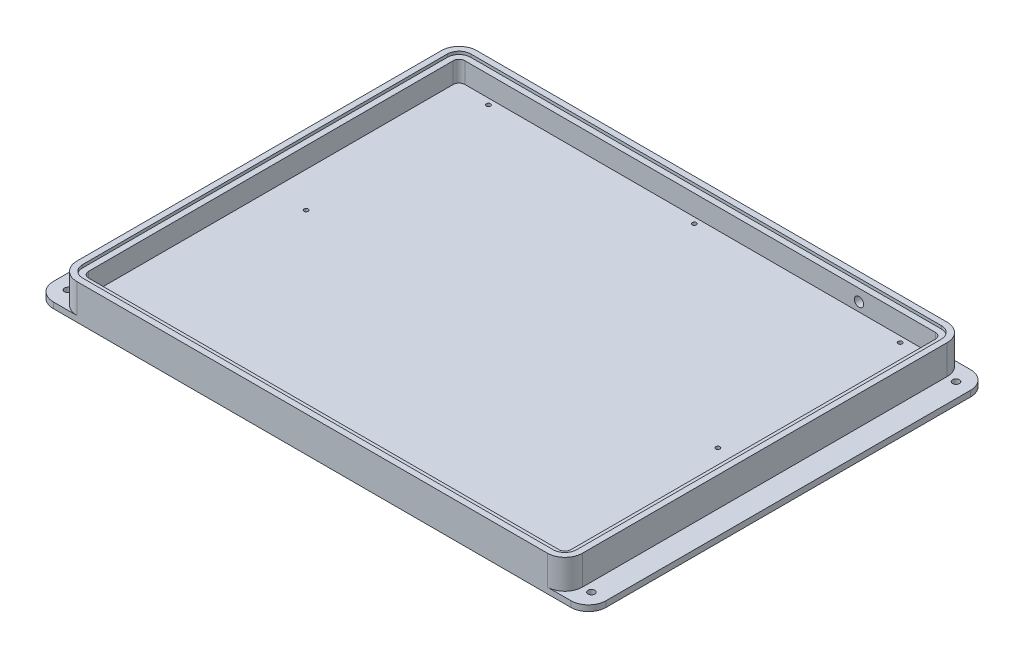
SolidWorks part; units mm, degrees
ref_plane "Front Plane" through (0, 0, 0) normal (0, 0, 1) x (1, 0, 0)
ref_plane "Top Plane" through (0, 0, 0) normal (0, 1, 0) x (1, 0, 0)
ref_plane "Right Plane" through (0, 0, 0) normal (1, 0, 0) x (0, 0, -1)
sketch "Sketch1" plane through (0, 0, 0) normal (0, 1, 0) x (1, 0, 0)
  line L1 (0, 0) -> (273.05, 0)
  line L2 (0, 0) -> (0, 215.9)
  line L3 (0, 215.9) -> (273.05, 215.9)
  line L4 (273.05, 0) -> (273.05, 215.9)
  dimension "D1" = 273.05
  dimension "D2" = 215.9
extrude "Boss-Extrude1" add sketch "Sketch1" along normal blind 19.05
fillet "Fillet1" radius 9.525 4 edges at (273.05, 9.525, 0) (273.05, 9.525, -215.9) (0, 9.525, 0) (0, 9.525, -215.9)
sketch "Sketch3" plane through (0, 19.05, 0) normal (0, 1, 0) x (1, 0, 0)
  line L25 (266.7, 9.525) -> (266.7, 206.375)
  line L26 (9.525, 6.35) -> (263.525, 6.35)
  line L27 (6.35, 206.375) -> (6.35, 9.525)
  line L28 (263.525, 209.55) -> (9.525, 209.55)
  line L29 (266.7, 9.525) -> (266.7, 206.375)
  line L30 (9.525, 6.35) -> (263.525, 6.35)
  line L31 (6.35, 206.375) -> (6.35, 9.525)
  line L32 (263.525, 209.55) -> (9.525, 209.55)
  arc A21 (266.7, 206.375) -> (263.525, 209.55) centre (263.525, 206.375) ccw
  arc A22 (263.525, 6.35) -> (266.7, 9.525) centre (263.525, 9.525) ccw
  arc A23 (6.35, 9.525) -> (9.525, 6.35) centre (9.525, 9.525) ccw
  arc A24 (9.525, 209.55) -> (6.35, 206.375) centre (9.525, 206.375) ccw
  arc A25 (266.7, 206.375) -> (263.525, 209.55) centre (263.525, 206.375) ccw
  arc A26 (263.525, 6.35) -> (266.7, 9.525) centre (263.525, 9.525) ccw
  arc A27 (6.35, 9.525) -> (9.525, 6.35) centre (9.525, 9.525) ccw
  arc A28 (9.525, 209.55) -> (6.35, 206.375) centre (9.525, 206.375) ccw
  dimension "D1" = 6.35
extrude "Cut-Extrude1" cut sketch "Sketch3" against normal blind 12.7
sketch "Sketch4" plane through (0, 19.05, 0) normal (0, 1, 0) x (1, 0, 0)
  line L24 (269.875, 9.525) -> (269.875, 206.375)
  line L25 (9.525, 3.175) -> (263.525, 3.175)
  line L26 (3.175, 206.375) -> (3.175, 9.525)
  line L27 (263.525, 212.725) -> (9.525, 212.725)
  line L28 (269.875, 9.525) -> (269.875, 206.375)
  line L29 (9.525, 3.175) -> (263.525, 3.175)
  line L30 (3.175, 206.375) -> (3.175, 9.525)
  line L31 (263.525, 212.725) -> (9.525, 212.725)
  arc A20 (269.875, 206.375) -> (263.525, 212.725) centre (263.525, 206.375) ccw
  arc A21 (263.525, 3.175) -> (269.875, 9.525) centre (263.525, 9.525) ccw
  arc A22 (3.175, 9.525) -> (9.525, 3.175) centre (9.525, 9.525) ccw
  arc A23 (9.525, 212.725) -> (3.175, 206.375) centre (9.525, 206.375) ccw
  arc A24 (269.875, 206.375) -> (263.525, 212.725) centre (263.525, 206.375) ccw
  arc A25 (263.525, 3.175) -> (269.875, 9.525) centre (263.525, 9.525) ccw
  arc A26 (3.175, 9.525) -> (9.525, 3.175) centre (9.525, 9.525) ccw
  arc A27 (9.525, 212.725) -> (3.175, 206.375) centre (9.525, 206.375) ccw
  dimension "D1" = 3.175
extrude "Cut-Extrude2" cut sketch "Sketch4" against normal blind 1.5875
sketch "Sketch5" plane through (0, 6.35, 0) normal (0, 1, 0) x (1, 0, 0)
  line L0 (136.525, 206.375) -> (136.525, 209.55) construction
  line L1 (25.4, 206.375) -> (247.65, 206.375) construction
  line L2 (25.4, 206.375) -> (25.4, 9.525) construction
  line L3 (25.4, 9.525) -> (247.65, 9.525) construction
  line L4 (247.65, 206.375) -> (247.65, 9.525) construction
  line L5 (263.525, 209.55) -> (9.525, 209.55) construction
  line L6 (25.4, 107.95) -> (6.35, 107.95) construction
  line L7 (6.35, 206.375) -> (6.35, 9.525) construction
  line L8 (247.65, 107.95) -> (266.7, 107.95) construction
  line L9 (266.7, 9.525) -> (266.7, 206.375) construction
  line L10 (136.525, 9.525) -> (136.525, 6.35) construction
  line L11 (263.525, 6.35) -> (9.525, 6.35) construction
  circle A0 centre (25.4, 206.375) radius 1.1303
  circle A1 centre (136.525, 206.375) radius 1.1303
  circle A2 centre (247.65, 206.375) radius 1.1303
  circle A3 centre (247.65, 107.95) radius 1.1303
  circle A4 centre (25.4, 107.95) radius 1.1303
  circle A5 centre (25.4, 9.525) radius 1.1303
  circle A6 centre (136.525, 9.525) radius 1.1303
  circle A7 centre (247.65, 9.525) radius 1.1303
  dimension "D3" = 2.2606
  dimension "D1" = 196.85
  dimension "D2" = 222.25
extrude "Cut-Extrude3" cut sketch "Sketch5" against normal blind 4.7625
sketch "Sketch6" plane through (0, 0, -215.9) normal (0, 0, -1) x (-1, 0, 0)
  line L1 (-273.05, 0) -> (-273.05, 19.05) construction
  line L3 (-263.525, 19.05) -> (-9.525, 19.05) construction
  circle A0 centre (-222.25, 11.1125) radius 2.5
  dimension "D2" = 5
  dimension "D1" = 50.8
  dimension "D3" = 7.9375
extrude "Cut-Extrude4" cut sketch "Sketch6" against normal blind 12.7
sketch "Sketch7" plane through (0, 0, 0) normal (0, -1, 0) x (1, 0, 0)
  line L0 (263.525, -215.9) -> (9.525, -215.9) construction
  line L1 (-3.175, 0) -> (276.225, 0)
  line L2 (-12.7, -9.525) -> (-12.7, -206.375)
  line L3 (-3.175, -215.9) -> (276.225, -215.9)
  line L4 (285.75, -9.525) -> (285.75, -206.375)
  line L5 (9.525, 0) -> (263.525, 0) construction
  line L6 (0, -206.375) -> (0, -9.525) construction
  line L7 (273.05, -9.525) -> (273.05, -206.375) construction
  arc A0 (-12.7, -206.375) -> (-3.175, -215.9) centre (-3.175, -206.375) ccw
  arc A1 (276.225, -215.9) -> (285.75, -206.375) centre (276.225, -206.375) ccw
  arc A2 (276.225, 0) -> (285.75, -9.525) centre (276.225, -9.525) cw
  arc A3 (-3.175, 0) -> (-12.7, -9.525) centre (-3.175, -9.525) ccw
  dimension "D3" = 9.525
  dimension "D1" = 12.7
  dimension "D2" = 12.7
extrude "Boss-Extrude2" add sketch "Sketch7" against normal blind 3.175
sketch "Sketch8" plane through (0, 3.175, 0) normal (0, 1, 0) x (1, 0, 0)
  line L0 (-4.7625, 215.9) -> (-4.7625, 0) construction
  line L1 (-12.7, 9.525) -> (-12.7, 206.375) construction
  line L2 (-3.175, 215.9) -> (9.525, 215.9) construction
  line L3 (285.75, 206.375) -> (285.75, 9.525) construction
  line L4 (-4.7625, 206.375) -> (277.8125, 206.375) construction
  line L5 (-4.7625, 206.375) -> (-4.7625, 9.525) construction
  line L6 (-4.7625, 9.525) -> (277.8125, 9.525) construction
  line L7 (277.8125, 206.375) -> (277.8125, 9.525) construction
  line L8 (9.525, 0) -> (-3.175, 0) construction
  circle A0 centre (-4.7625, 206.375) radius 1.8288
  circle A1 centre (-4.7625, 9.525) radius 1.8288
  circle A2 centre (277.8125, 9.525) radius 1.8288
  circle A3 centre (277.8125, 206.375) radius 1.8288
  dimension "D2" = 3.6576
  dimension "D1" = 7.9375
  dimension "D3" = 9.525
  dimension "D4" = 7.9375
  dimension "D5" = 9.525
extrude "Cut-Extrude5" cut sketch "Sketch8" against normal through all
